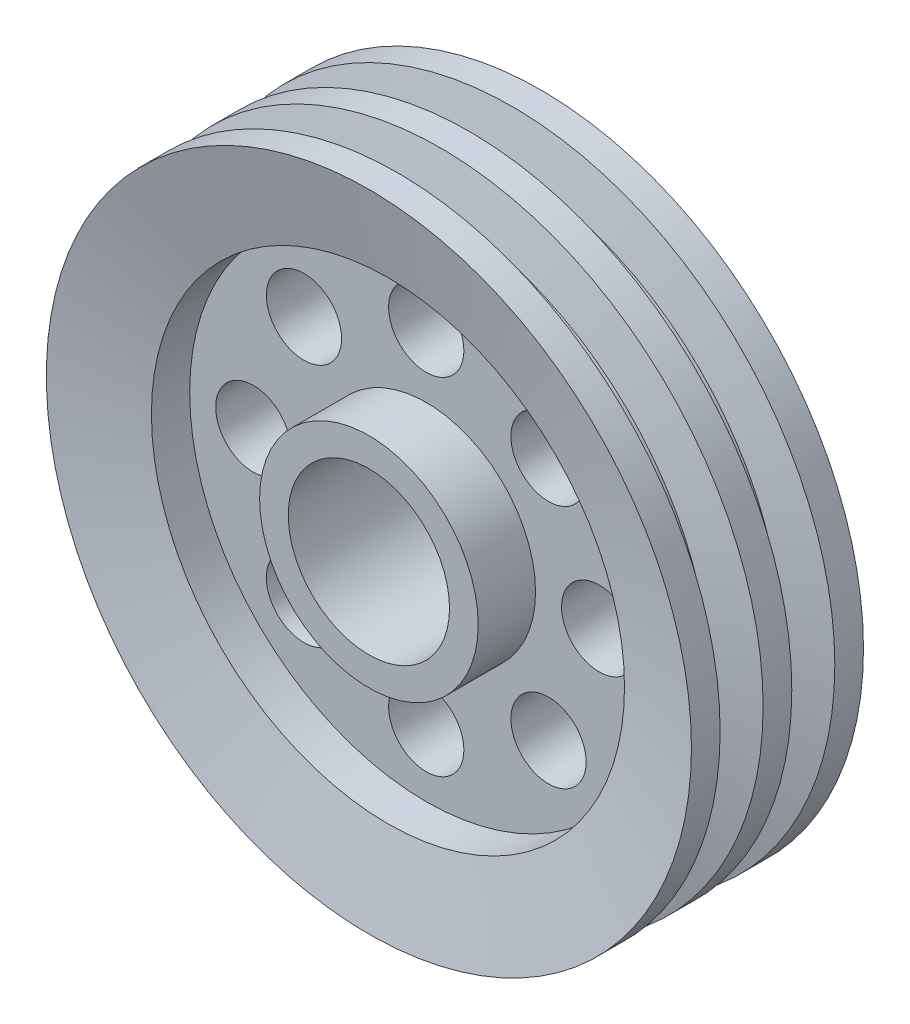
SolidWorks part; units mm, degrees
material "Plain Carbon Steel"
ref_plane "Front Plane" through (0, 0, 0) normal (0, 0, 1) x (1, 0, 0)
ref_plane "Top Plane" through (0, 0, 0) normal (0, 1, 0) x (1, 0, 0)
ref_plane "Right Plane" through (0, 0, 0) normal (1, 0, 0) x (0, 0, -1)
sketch "Sketch1" plane through (0, 0, 0) normal (0, 0, 1) x (1, 0, 0)
  line L0 (0, 150) -> (0, -150) construction
  line L1 (-150, 0) -> (150, 0) construction
  line L2 (0, 50.8333) -> (0, 110)
  circle A0 centre (0, 0) radius 37.5
  circle A1 centre (0, 0) radius 50.8333
  circle A2 centre (0, 0) radius 110
  circle A3 centre (0, 0) radius 150
  circle A5 centre (0, 80.4167) radius 17.5
  circle A6 centre (56.8632, 56.8632) radius 17.5
  circle A7 centre (80.4167, 0) radius 17.5
  circle A8 centre (56.8632, -56.8632) radius 17.5
  circle A9 centre (0, -80.4167) radius 17.5
  circle A10 centre (-56.8632, -56.8632) radius 17.5
  circle A11 centre (-80.4167, 0) radius 17.5
  circle A12 centre (-56.8632, 56.8632) radius 17.5
  point P15 (84.5957, 0)
  point P16 (0, -81.412)
  point P30 (0, 0)
  dimension "D1" = 300
  dimension "D2" = 75
  dimension "D5" = 35
  dimension "D3" = 13.3333
  dimension "D4" = 40
  dimension "D6" = 8
extrude "Boss-Extrude1" add sketch "Sketch1" along normal mid plane 80 contours A3 A2 | A1 A0 region at (34.9279, 34.9279, 0) region at (-145.7574, 0, 0)
extrude "Boss-Extrude2" add sketch "Sketch1<3>" along normal mid plane 26.6667 contours A5 A2 A1 A12 A11 A10 A9 A8 A7 A6 region at (75.5817, 75.5817, 0)
sketch "Sketch1<3>" plane through (0, 0, 0) normal (0, 0, 1) x (1, 0, 0) same geometry as "Sketch1"
sketch "Sketch2" plane through (0, 0, 0) normal (1, 0, 0) x (0, 0, -1)
  line L0 (0, 0) -> (0, 107.9188) construction
  line L1 (-40, 150) -> (-26.6667, 150)
  line L2 (-40, 150) -> (-40, -150) construction
  line L3 (-26.6667, 150) -> (-22.2328, 130)
  line L4 (-22.2328, 130) -> (-11.1006, 130)
  line L5 (-11.1006, 130) -> (-6.6667, 150)
  line L6 (40, 150) -> (-40, 150) construction
  line L7 (-6.6667, 150) -> (6.6667, 150)
  line L8 (-40, 150) -> (-31.1322, 110)
  line L9 (-31.1322, 110) -> (-40, 110)
  line L10 (-40, 110) -> (-40, 150)
  line L11 (11.1006, 130) -> (6.6667, 150)
  line L12 (22.2328, 130) -> (11.1006, 130)
  line L13 (26.6667, 150) -> (22.2328, 130)
  line L14 (40, 150) -> (26.6667, 150)
  line L15 (31.1322, 110) -> (40, 110)
  line L16 (40, 150) -> (31.1322, 110)
  line L17 (40, 110) -> (40, 150)
  line L18 (-26.6667, 150) -> (-6.6667, 150)
  line L19 (6.6667, 150) -> (26.6667, 150)
  line L20 (-46.0274, 0) -> (90.9589, 0) construction
  line L21 (-26.6667, 150) -> (-22.2328, 130)
  line L22 (-11.1006, 130) -> (-6.6667, 150)
  line L23 (2.2011, 190) -> (-35.5345, 190)
  line L24 (-35.5345, 190) -> (-26.6667, 150)
  line L25 (2.2011, 190) -> (-6.6667, 150)
  point P16 (0, 150)
  dimension "D3" = 13.3333
  dimension "D1" = 25
  dimension "D2" = 40
  dimension "D4" = 20
  dimension "D5" = 150
  dimension "D6" = 60
revolve "Cut-Revolve2" cut sketch "Sketch2" angle 360 about L20
revolve "Cut-Revolve3" cut sketch "Sketch2<5>" angle 360 about L20
sketch "Sketch2<5>" plane through (0, 0, 0) normal (1, 0, 0) x (0, 0, -1) same geometry as "Sketch2"
revolve "Cut-Revolve5" cut sketch "Sketch2<7>" angle 360 about L20 region at (0, 140.9495, 16.6667)
sketch "Sketch2<7>" plane through (0, 0, 0) normal (1, 0, 0) x (0, 0, -1) same geometry as "Sketch2"
mirror "Mirror1" about plane through (0, 0, 0) normal (0, 0, 1) of "Cut-Revolve5"
equation "\"A\" = 300"
equation "\"D1@Sketch1\"=\"A\""
equation "\"D2@Sketch1\"=\"A\"/4"
equation "\"B\" = 80"
equation "\"D3@Sketch1\"=\"B\"/6"
equation "\"D4@Sketch1\"=\"B\"/2"
equation "\"C\"= 35"
equation "\"D5@Sketch1\"=\"C\""
equation "\"D1@Boss-Extrude1\"=\"B\""
equation "\"D1@Boss-Extrude2\"=\"B\"/3"
equation "\"D2@Sketch2\"=\"B\"/2"
equation "\"D3@Sketch2\"=\"B\"/6"
equation "\"D4@Sketch2\"=\"B\"/4"
equation "\"D5@Sketch2\"=\"A\"/2"
